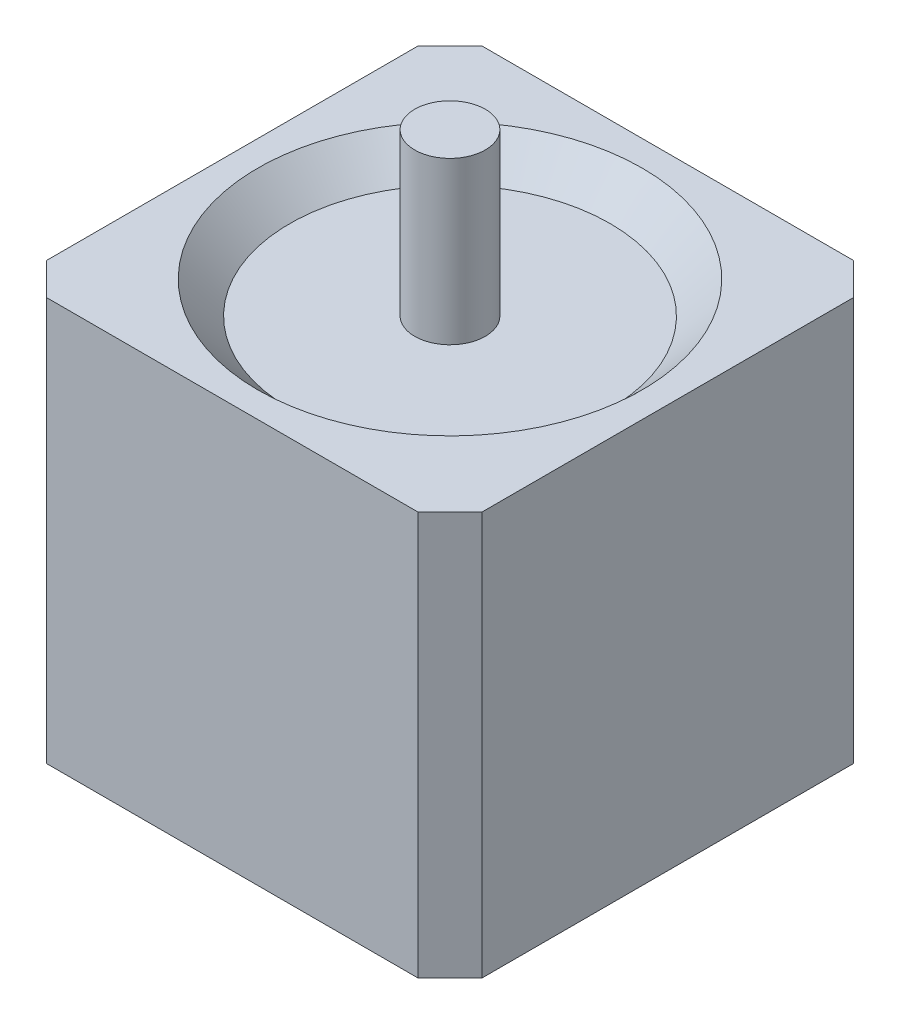
SolidWorks part; units mm, degrees
ref_plane "Front Plane" through (0, 0, 0) normal (0, 0, 1) x (1, 0, 0)
ref_plane "Top Plane" through (0, 0, 0) normal (0, 1, 0) x (1, 0, 0)
ref_plane "Right Plane" through (0, 0, 0) normal (1, 0, 0) x (0, 0, -1)
sketch "Sketch1" plane through (0, 0, 0) normal (0, 1, 0) x (1, 0, 0)
  line L1 (-43.18, -43.18) -> (43.18, -43.18)
  line L2 (-43.18, -43.18) -> (-43.18, 43.18)
  line L3 (-43.18, 43.18) -> (43.18, 43.18)
  line L4 (43.18, -43.18) -> (43.18, 43.18)
  line L5 (-43.18, -43.18) -> (43.18, 43.18) construction
  line L6 (-43.18, 43.18) -> (43.18, -43.18) construction
  point P0 (0, 0)
  dimension "D1" = 86.36
  dimension "D2" = 86.36
extrude "Boss-Extrude1" add sketch "Sketch1" along normal blind 80.01
sketch "Sketch2" plane through (0, 80.01, 0) normal (0, 1, 0) x (1, 0, 0)
  circle A0 centre (0, 0) radius 31.75
  dimension "D1" = 63.5
extrude "Cut-Extrude1" cut sketch "Sketch2" against normal blind 6.35
chamfer "Chamfer1" distance 6.35 angle 45 4 edges at (43.18, 40.005, 43.18) (-43.18, 40.005, 43.18) (-43.18, 40.005, -43.18) (43.18, 40.005, -43.18)
sketch "Sketch3" plane through (0, 73.66, 0) normal (0, 1, 0) x (1, 0, 0)
  circle A0 centre (0, 0) radius 6.999
  dimension "D1" = 13.9979
extrude "Boss-Extrude2" add sketch "Sketch3" along normal blind 32.004
chamfer "Chamfer2" distance 6.35 angle 45 1 edges at (0, 80.01, 31.75)
